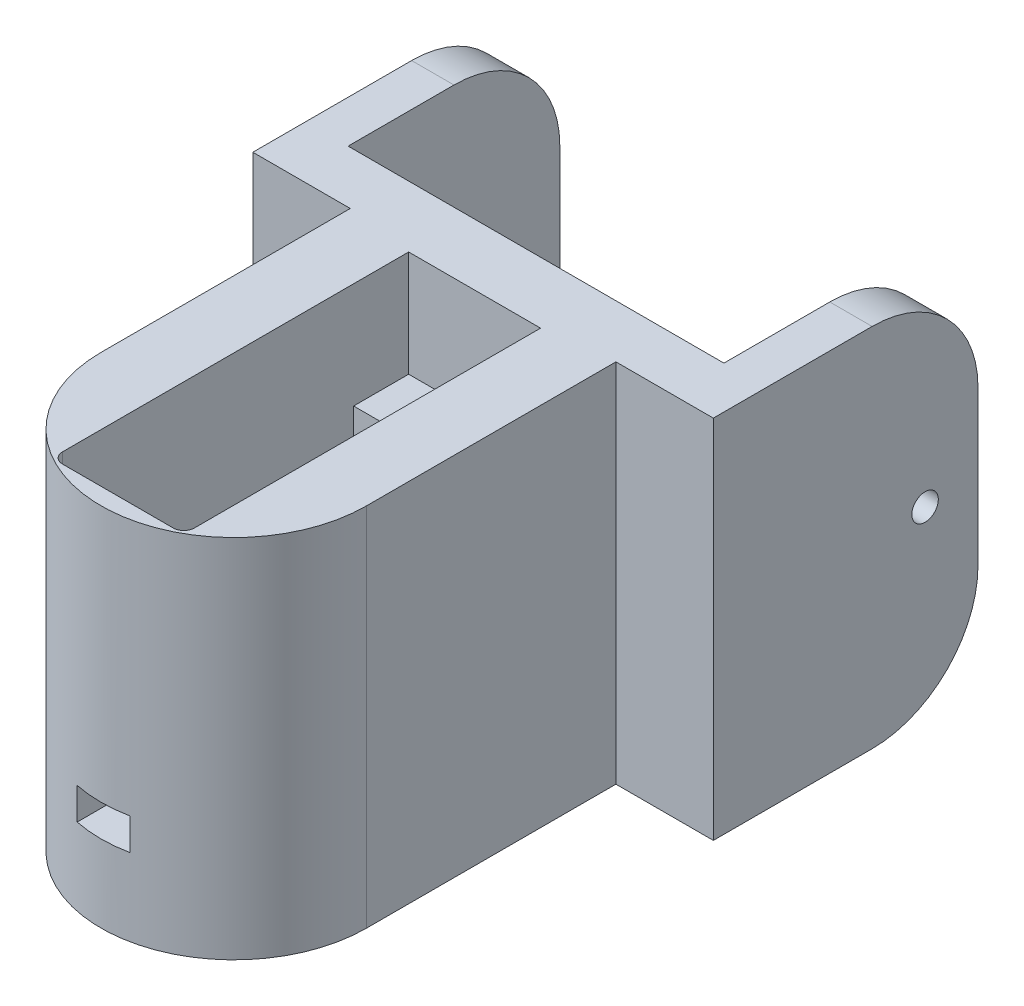
SolidWorks part; units mm, degrees
ref_plane "Front Plane" through (0, 0, 0) normal (0, 0, 1) x (1, 0, 0)
ref_plane "Top Plane" through (0, 0, 0) normal (0, 1, 0) x (1, 0, 0)
ref_plane "Right Plane" through (0, 0, 0) normal (1, 0, 0) x (0, 0, -1)
sketch "Sketch4" plane through (0, 0, 0) normal (0, 0, 1) x (1, 0, 0)
  line L1 (-6.23, -9.975) -> (6.23, -9.975)
  line L2 (-6.23, -9.975) -> (-6.23, 7.275)
  line L3 (-6.23, 7.275) -> (6.23, 7.275)
  line L4 (6.23, -9.975) -> (6.23, 7.275)
  point P4 (0, 7.275)
  dimension "D1" = 12.46
  dimension "D2" = 17.25
  dimension "D3" = 9.975
extrude "Boss-Extrude3" add sketch "Sketch4" along normal blind 6
sketch "Sketch8" plane through (0, -9.975, 0) normal (0, -1, 0) x (-1, 0, 0)
  circle A0 centre (0, -23.55) radius 12.5468
  circle A1 centre (0, -23.55) radius 11.15
  dimension "D1" = 22.3
  dimension "D2" = 23.55
extrude "Boss-Extrude6" add sketch "Sketch8" along normal blind 7.3 and the other way up to surface (17.25 mm away) other way up to face at (0, 7.275, 3)
sketch "Sketch5" plane through (0, 7.275, 0) normal (0, 1, 0) x (1, 0, 0)
  line L8 (12.5468, -23.55) -> (12.5468, 0)
  line L9 (12.5468, 0) -> (6.23, 0)
  line L10 (-12.5468, -23.55) -> (-12.5468, 0)
  line L11 (-12.5468, 0) -> (-6.23, 0)
  line L12 (-6.23, 0) -> (-6.23, -29.7)
  line L14 (6.23, -29.7) -> (6.23, 0)
  line L15 (-6.23, -29.7) -> (6.23, -29.7)
  line L16 (6.23, -6) -> (-6.23, -6) construction
  circle A0 centre (0, -23.55) radius 12.5468 construction
  arc A1 (-12.5468, -23.55) -> (12.5468, -23.55) centre (0, -23.55) ccw
  dimension "D1" = 23.7
  dimension "D2" = 23.55
extrude "Boss-Extrude4" add sketch "Sketch5" against normal up to surface (17.25 mm away) up to face at (0, -9.975, 3)
sketch "Sketch6" plane through (0, 7.275, 0) normal (0, 1, 0) x (1, 0, 0)
  line L0 (6.23, -6) -> (-6.23, -6) construction
  line L3 (6.23, -29.7) -> (-6.23, -29.7) construction
  circle A0 centre (0, -3.6) radius 0.5
  circle A1 centre (0, -32.1) radius 0.5
  dimension "D1" = 1
  dimension "D3" = 1
  dimension "D2" = 2.4
  dimension "D4" = 2.4
extrude "Cut-Extrude1" cut sketch "Sketch6" against normal blind 5
chamfer "Chamfer1" distance 0.5 angle 60 2 edges at (0, 7.275, 4.1) (0, 7.275, 32.6) first distance on face at (0, 7.275, 4.1)
sketch "Sketch10" plane through (0, 7.275, 0) normal (0, 1, 0) x (1, 0, 0)
  line L1 (-6.23, -6) -> (6.23, -6)
  line L2 (-6.23, -6) -> (-6.23, -29.7)
  line L3 (-6.23, -29.7) -> (6.23, -29.7)
  line L4 (6.23, -6) -> (6.23, -29.7)
extrude "Cut-Extrude3" cut sketch "Sketch10" against normal up to surface (17.25 mm away) up to face at (0, -9.975, 10.3399)
ref_plane "Plane1" through (0, 0, 36.0968) normal (0, 0, 1) x (1, 0, 0)
sketch "Sketch11" plane through (0, 0, 36.0968) normal (0, 0, 1) x (1, 0, 0)
  line L0 (-11.15, -9.975) -> (11.15, -9.975) construction
  line L1 (-2.5, -6.975) -> (2.5, -6.975)
  line L2 (-2.5, -6.975) -> (-2.5, -9.975)
  line L3 (-2.5, -9.975) -> (2.5, -9.975)
  line L4 (2.5, -6.975) -> (2.5, -9.975)
  point P4 (0, -6.975)
  dimension "D1" = 0
  dimension "D2" = 5
  dimension "D3" = 3
extrude "Cut-Extrude4" cut sketch "Sketch11" against normal up to next
sketch "Sketch13" plane through (0, -17.275, 0) normal (0, -1, 0) x (1, 0, 0)
  line L0 (-12.5468, 23.55) -> (-12.5468, 0)
  line L1 (-12.5468, 0) -> (12.5468, 0)
  line L2 (12.5468, 0) -> (12.5468, 23.55)
  arc A0 (-12.5468, 23.55) -> (12.5468, 23.55) centre (0, 23.55) ccw
  point P3 (0, 0)
extrude "Boss-Extrude7" add sketch "Sketch13" against normal up to surface (7.3 mm away) up to face at (0, -9.975, 10.3399)
sketch "Sketch15" plane through (0, 7.275, 0) normal (0, 1, 0) x (1, 0, 0)
  line L0 (-12.5468, 0) -> (12.5468, 0)
  line L1 (12.5468, 0) -> (12.5468, -23.55)
  line L2 (-12.5468, 0) -> (-12.5468, -23.55)
  line L3 (6.23, -6) -> (6.23, -29.7) construction
  line L4 (-6.23, -0.8) -> (6.23, -0.8)
  line L5 (-6.23, -0.8) -> (-6.23, -33.5)
  line L6 (-5.23, -34.5) -> (5.23, -34.5)
  line L7 (6.23, -0.8) -> (6.23, -33.5)
  arc A0 (-12.5468, -23.55) -> (12.5468, -23.55) centre (0, -23.55) ccw
  circle A1 centre (0, -3.6) radius 0.5 construction
  arc A2 (5.23, -34.5) -> (6.23, -33.5) centre (5.23, -33.5) ccw
  arc A3 (-6.23, -33.5) -> (-5.23, -34.5) centre (-5.23, -33.5) ccw
  point P15 (0, -0.8)
  dimension "D1" = 0.8
  dimension "D3" = 1
  dimension "D2" = 2.8
  dimension "D4" = 0
  dimension "D5" = 34.5
extrude "Boss-Extrude9" add sketch "Sketch15" along normal blind 10
sketch "Sketch20" plane through (0, -17.275, 0) normal (0, -1, 0) x (1, 0, 0)
  circle A0 centre (0, 23.55) radius 7.15
  circle A1 centre (0, 23.55) radius 11.15
  circle A2 centre (0, 23.55) radius 11.15 construction
  dimension "D1" = 14.3
extrude "Boss-Extrude11" add sketch "Sketch20" against normal up to surface (7.3 mm away) up to face at (-6.0145, -9.975, 27.3356)
sketch "Sketch21" plane through (0, -17.275, 0) normal (0, -1, 0) x (1, 0, 0)
  circle A0 centre (0, 23.55) radius 7.15
  circle A1 centre (0, 23.55) radius 10.15
  circle A2 centre (0, 23.55) radius 7.15 construction
  dimension "D1" = 20.3
extrude "Cut-Extrude7" cut sketch "Sketch21" against normal blind 1.3
sketch "Sketch17" plane through (0, 17.275, 0) normal (0, 1, 0) x (1, 0, 0)
  line L0 (21.75, 25) -> (21.75, 0)
  line L1 (21.75, 0) -> (-21.75, 0)
  line L2 (-21.75, 0) -> (-21.75, 25)
  line L3 (-21.75, 25) -> (-17.75, 25)
  line L4 (-17.75, 25) -> (-17.75, 5)
  line L5 (-17.75, 5) -> (17.75, 5)
  line L6 (17.75, 5) -> (17.75, 25)
  line L7 (17.75, 25) -> (21.75, 25)
  point P2 (0, 5)
  point P10 (0, 0)
  dimension "D1" = 4
  dimension "D2" = 35.5
  dimension "D3" = 0
  dimension "D4" = 25
  dimension "D5" = 5
extrude "Boss-Extrude10" add sketch "Sketch17" against normal up to surface (34.55 mm away) up to face at (0, -17.275, 13.4)
sketch "Sketch18" plane through (17.75, 0, 0) normal (-1, 0, 0) x (0, 0, 1)
  line L0 (-25, -17.275) -> (-25, 17.275) construction
  line L1 (-25, 6.2191) -> (-5, 6.2191)
  line L2 (-25, 6.2191) -> (-25, -6.2191)
  line L3 (-25, -6.2191) -> (-5, -6.2191)
  line L4 (-5, 6.2191) -> (-5, -6.2191)
  line L5 (-5, -17.275) -> (-5, 17.275) construction
  point P6 (-25, 0)
  point P7 (-25, 0)
  dimension "D1" = 0
extrude "Cut-Extrude5" cut sketch "Sketch18" against normal blind 2
sketch "Sketch19" plane through (19.75, 0, 0) normal (-1, 0, 0) x (0, 0, 1)
  line L0 (-25, -17.275) -> (-25, 17.275) construction
  circle A0 centre (-20, 0) radius 1.25
  dimension "D1" = 2.5
  dimension "D2" = 5
extrude "Cut-Extrude6" cut sketch "Sketch19" against normal through all both and the other way through all
fillet "Fillet1" radius 10 4 edges at (19.75, -17.275, -25) (19.75, 17.275, -25) (-19.75, 17.275, -25) (-19.75, -17.275, -25)
ref_plane "Plane2" through (0, 0, 0) normal (1, 0, 0) x (0, 0, -1)
ref_plane "Plane3" through (0, 0, 0) normal (0, -1, 0) x (-1, 0, 0)
